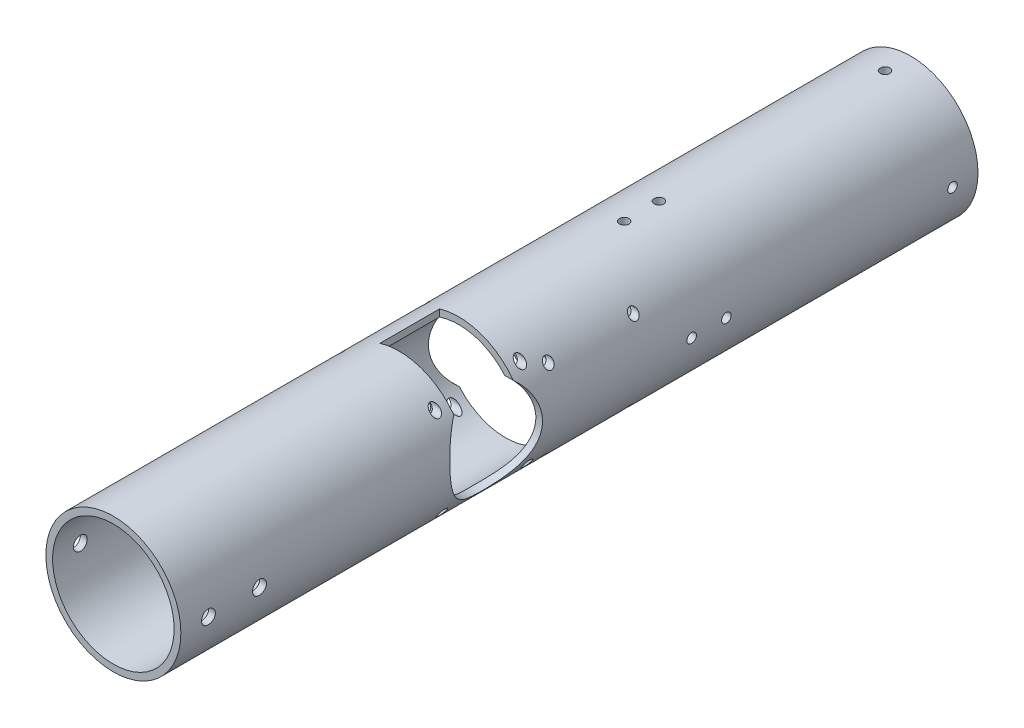
SolidWorks part; units mm, degrees
material "6061 Alloy"
ref_plane "Front Plane" through (0, 0, 0) normal (0, 0, 1) x (1, 0, 0)
ref_plane "Top Plane" through (0, 0, 0) normal (0, 1, 0) x (1, 0, 0)
ref_plane "Right Plane" through (0, 0, 0) normal (1, 0, 0) x (0, 0, -1)
sketch "Sketch1" plane through (0, 0, 0) normal (0, 0, 1) x (1, 0, 0)
  circle A0 centre (0, 0) radius 31.75
  circle A1 centre (0, 0) radius 28.575
  dimension "D1" = 63.5
  dimension "D2" = 57.15
extrude "Boss-Extrude1" add sketch "Sketch1" along normal blind 125 and the other way blind 250 contours A1 | A0 region at (0, 0, 0)
sketch "Sketch2" plane through (0, 0, 0) normal (1, 0, 0) x (0, 0, -1)
  circle A2 centre (73.488, -2) radius 21.75
  dimension "D1" = 43.5
  dimension "D2" = 73.488
  dimension "D3" = 2
extrude "Cut-Extrude1" cut sketch "Sketch2" against normal through all
sketch "Sketch3" plane through (0, 0, 0) normal (1, 0, 0) x (0, 0, -1)
  circle A1 centre (23.45, 2) radius 21.75
  dimension "D1" = 23.45
  dimension "D2" = 43.5
  dimension "D3" = 2
extrude "Cut-Extrude2" cut sketch "Sketch3" along normal through all
sketch "Sketch5" plane through (0, 0, 0) normal (1, 0, 0) x (0, 0, -1)
  line L1 (87.488, -12.75) -> (59.488, -12.75)
  line L2 (87.488, -12.75) -> (87.488, -34.75)
  line L3 (87.488, -34.75) -> (59.488, -34.75)
  line L4 (59.488, -12.75) -> (59.488, -34.75)
  line L5 (87.488, -12.75) -> (59.488, -34.75) construction
  line L6 (87.488, -34.75) -> (59.488, -12.75) construction
  circle A0 centre (73.488, -2) radius 21.75 construction
  circle A1 centre (73.488, -2) radius 21.75 construction
  circle A2 centre (73.488, -2) radius 21.75 construction
  point P0 (73.488, -23.75)
  dimension "D1" = 28
  dimension "D2" = 22
extrude "Cut-Extrude4" cut sketch "Sketch5" against normal through all from offset 9
sketch "Sketch6" plane through (0, 0, 0) normal (1, 0, 0) x (0, 0, -1)
  line L1 (9.45, 34.75) -> (37.45, 34.75)
  line L2 (9.45, 34.75) -> (9.45, 12.75)
  line L3 (9.45, 12.75) -> (37.45, 12.75)
  line L4 (37.45, 34.75) -> (37.45, 12.75)
  line L5 (9.45, 34.75) -> (37.45, 12.75) construction
  line L6 (9.45, 12.75) -> (37.45, 34.75) construction
  circle A0 centre (23.45, 2) radius 21.75 construction
  circle A1 centre (23.45, 2) radius 21.75 construction
  circle A2 centre (23.45, 2) radius 21.75 construction
  point P0 (23.45, 23.75)
  dimension "D1" = 28
  dimension "D2" = 22
extrude "Cut-Extrude5" cut sketch "Sketch6" along normal through all from offset 9 offset against normal yes
sketch "Sketch10" plane through (0, 0, 0) normal (1, 0, 0) x (0, 0, -1)
  line L1 (113.488, 38) -> (33.488, 38)
  line L2 (113.488, 38) -> (113.488, -42)
  line L3 (113.488, -42) -> (33.488, -42)
  line L4 (33.488, 38) -> (33.488, -42)
  line L5 (113.488, 38) -> (33.488, -42) construction
  line L6 (113.488, -42) -> (33.488, 38) construction
  point P0 (73.488, -2)
  dimension "D1" = 80
  dimension "D2" = 80
sketch "Sketch11" plane through (0, 0, 0) normal (1, 0, 0) x (0, 0, -1)
  line L0 (113.488, 38) -> (33.488, -42) construction
  line L1 (113.488, -42) -> (33.488, 38) construction
  line L2 (51.738, -2) -> (95.238, -2) construction
  line L3 (53.488, 18) -> (53.488, -22) construction
  circle A0 centre (93.488, 18) radius 2
  circle A1 centre (53.488, 18) radius 2
  circle A2 centre (53.488, -22) radius 2
  circle A3 centre (93.488, -22) radius 2
  arc A4 (87.488, -18.6452) -> (59.488, -18.6452) centre (73.488, -2) ccw construction
  arc A5 (87.488, -18.6452) -> (59.488, -18.6452) centre (73.488, -2) ccw construction
  point P18 (53.488, -2)
  dimension "D5" = 4
  dimension "D1" = 40
extrude "Cut-Extrude8" cut sketch "Sketch11" against normal through all both and the other way through all
sketch "Sketch12" plane through (0, 0, 0) normal (1, 0, 0) x (0, 0, -1)
  line L0 (-125, 31.75) -> (-125, -31.75) construction
  circle A0 centre (-112, 0) radius 3.25
  circle A1 centre (-88, 0) radius 3.25
  dimension "D2" = 6.5
  dimension "D3" = 24
  dimension "D4" = 13
extrude "Cut-Extrude10" cut sketch "Sketch12" against normal through all both and the other way through all
sketch "Sketch13" plane through (0, 0, 0) normal (0, 1, 0) x (1, 0, 0)
  line L0 (0, -34.925) -> (0, 34.925) construction
  line L1 (28.575, 250) -> (-28.575, 250) construction
  line L2 (0, 250) -> (0, -125) construction
  circle A0 centre (0, 238) radius 2.25
  circle A1 centre (0, 205.9) radius 2.25 construction
  dimension "D2" = 4.5
  dimension "D3" = 32.1
  dimension "D1" = 12
extrude "Cut-Extrude11" cut sketch "Sketch13" against normal through all both and the other way through all
sketch "Sketch14" plane through (0, 0, 0) normal (1, 0, 0) x (0, 0, -1)
  line L0 (3.45, -18) -> (3.45, 22) construction
  line L1 (-1.55, 27) -> (48.45, 27) construction
  line L2 (-1.55, 27) -> (-1.55, -23) construction
  line L3 (-1.55, -23) -> (48.45, -23) construction
  line L4 (48.45, 27) -> (48.45, -23) construction
  line L5 (-1.55, 27) -> (48.45, -23) construction
  line L6 (-1.55, -23) -> (48.45, 27) construction
  circle A0 centre (3.45, 22) radius 2
  circle A1 centre (43.45, 22) radius 2
  circle A2 centre (43.45, -18) radius 2
  circle A3 centre (3.45, -18) radius 2
  point P0 (23.45, 2)
  point P14 (3.45, 2)
  dimension "D5" = 4
  dimension "D1" = 40
  dimension "D2" = 50
sketch "Sketch15" plane through (0, 0, 0) normal (1, 0, 0) x (0, 0, -1)
  circle A0 centre (3.45, 22) radius 2
  circle A1 centre (43.45, 22) radius 2
  circle A2 centre (43.45, -18) radius 2
  circle A3 centre (3.45, -18) radius 2
  dimension "D1" = 4
extrude "Cut-Extrude12" cut sketch "Sketch15" against normal through all and the other way through all
hole_wizard "M4 Clearance Hole1" positions "Sketch18" profile "Sketch19" hole size "M4" standard "ANSI Metric" end condition through all
sketch "Sketch18" plane through (0, 0, 0) normal (1, 0, 0) x (0, 0, -1)
  circle A0 centre (3.45, 22) radius 2 construction
  circle A1 centre (43.45, 22) radius 2 construction
  circle A2 centre (3.45, -18) radius 2 construction
  circle A3 centre (43.45, -18) radius 2 construction
  point P0 (3.45, 22)
  point P2 (43.45, 22)
  point P4 (3.45, -18)
  point P6 (43.45, -18)
  point P20 (93.488, 18)
  point P23 (53.488, 18)
  point P26 (93.488, -22)
  point P29 (53.488, -22)
sketch "Sketch19" plane through (0, 22, -3.45) normal (0, 1, 0) x (0, 0, 1)
  line L0 (0, 0) -> (0, 31.75)
  line L1 (0, 31.75) -> (2.25, 31.75)
  line L2 (2.25, 31.75) -> (2.25, 0)
  line L5 (2.25, 0) -> (0, 0)
  line L11 (0, -6.35) -> (0, 107.95) construction
  dimension "Thru Hole Dia." = 4.5
  dimension "Thru Hole Depth" = 31.75
mirror "Mirror1" about plane through (0, 0, 0) normal (1, 0, 0) of "M4 Clearance Hole1"
sketch "Sketch21" plane through (0, 0, -250) normal (0, 0, -1) x (-1, 0, 0)
  circle A0 centre (0, 0) radius 30
  dimension "D1" = 60
extrude "Cut-Extrude14" cut sketch "Sketch21" against normal blind 7
pattern_circular "CirPattern1" count 2 every 90 about axis through (0, 0, -250) along (0, 0, 1) of "Cut-Extrude11"
sketch "Sketch22" plane through (0, 0, 0) normal (1, 0, 0) x (0, 0, -1)
  circle A0 centre (221.65, 0) radius 2.25 construction
  circle A1 centre (131.65, 0) radius 2.25
  circle A2 centre (115.3, 0) radius 2.25
  circle A3 centre (238, 0) radius 2.25 construction
  circle A4 centre (238, 0) radius 2.25 construction
  dimension "D1" = 16.35
  dimension "D2" = 106.35
  dimension "D3" = 122.7
extrude "Cut-Extrude15" cut sketch "Sketch22" along normal through all
pattern_circular "CirPattern2" count 4 over 360 about axis through (0, 0, -250) along (0, 0, 1) of "Cut-Extrude15"
sketch "Sketch23" plane through (0, 0, -243) normal (0, 0, -1) x (-1, 0, 0)
  circle A0 centre (0, 0) radius 28.575 construction
  circle A1 centre (0, 0) radius 30
  circle A2 centre (0, 0) radius 30
  circle A3 centre (0, 0) radius 28.575
  dimension "D1" = 0
extrude "Boss-Extrude2" add sketch "Sketch23" along normal up to surface (7 mm away) up to face at (-30, 0, -250)
